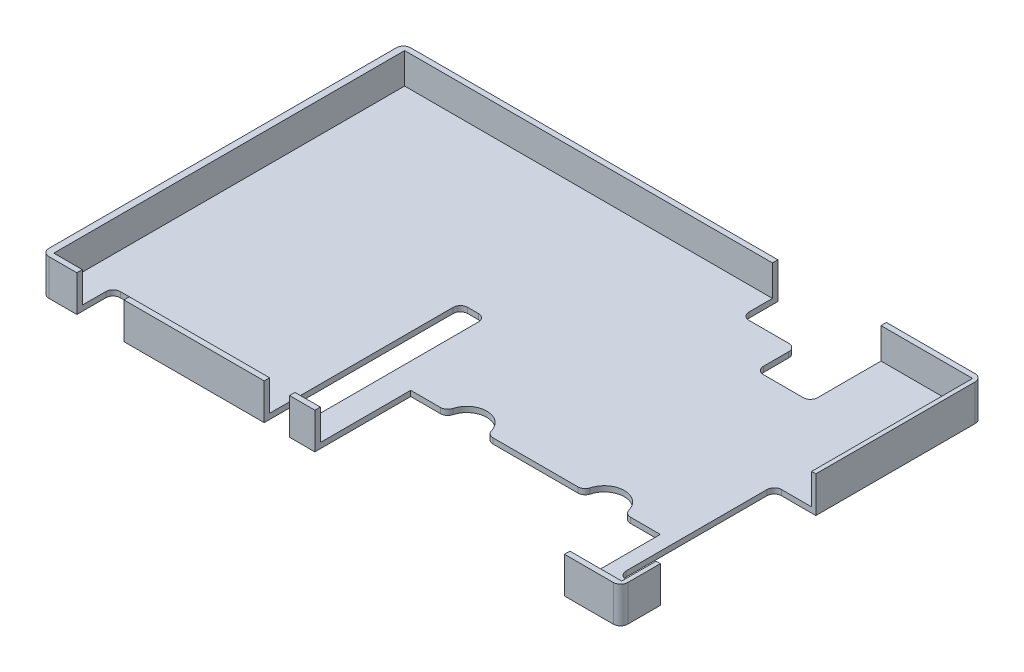
SolidWorks part; units mm, degrees
ref_plane "Front Plane" through (0, 0, 0) normal (0, 0, 1) x (1, 0, 0)
ref_plane "Top Plane" through (0, 0, 0) normal (0, 1, 0) x (1, 0, 0)
ref_plane "Right Plane" through (0, 0, 0) normal (1, 0, 0) x (0, 0, -1)
sketch "Sketch1" plane through (0, 0, 0) normal (0, 1, 0) x (1, 0, 0)
  line L1 (0, 0) -> (160, 0)
  line L2 (0, 0) -> (0, 100)
  line L3 (0, 100) -> (160, 100)
  line L4 (160, 0) -> (160, 100)
  dimension "D1" = 160
  dimension "D2" = 100
extrude "Boss-Extrude1" add sketch "Sketch1" along normal blind 1.5
sketch "Sketch2" plane through (0, 0, 0) normal (0, 1, 0) x (1, 0, 0)
  line L0 (160, 78.8862) -> (158.8264, 78.8862) construction
  line L1 (160, 0) -> (0, 0)
  line L2 (160, 0) -> (160, 100)
  line L3 (160, 100) -> (0, 100)
  line L4 (0, 0) -> (0, 100)
  line L5 (158.8264, 100) -> (158.8264, 98.5) construction
  line L7 (158.8264, 98.5) -> (1.8264, 98.5)
  line L8 (158.8264, 98.5) -> (158.8264, 1.5)
  line L9 (158.8264, 1.5) -> (1.8264, 1.5)
  line L10 (1.8264, 98.5) -> (1.8264, 1.5)
  dimension "D1" = 157
  dimension "D2" = 97
extrude "Boss-Extrude2" add sketch "Sketch2" along normal blind 10
fillet "Fillet1" radius 2 4 edges at (0, 5, -100) (160, 5, -100) (160, 5, 0) (0, 5, 0)
sketch "Sketch4" plane through (0, 0, 0) normal (0, -1, 0) x (1, 0, 0)
  line L0 (160, -94.7257) -> (133.5, -94.7257) construction
  line L1 (160, -2) -> (160, -98) construction
  line L2 (158, -100) -> (2, -100) construction
  line L3 (133.5, -100) -> (118.5, -100)
  line L4 (133.5, -100) -> (133.5, -79)
  line L5 (133.5, -79) -> (118.5, -79)
  line L6 (118.5, -100) -> (118.5, -79)
  dimension "D1" = 26.5
  dimension "D2" = 21
  dimension "D3" = 15
extrude "Cut-Extrude1" cut sketch "Sketch4" against normal through all
sketch "Sketch5" plane through (0, 0, 0) normal (0, -1, 0) x (1, 0, 0)
  line L0 (160, -9.2111) -> (144.5, -9.2111) construction
  line L1 (160, -2) -> (160, -98) construction
  line L2 (144.5, 0) -> (144.5, -26.5) construction
  line L3 (2, 0) -> (158, 0) construction
  line L5 (144.5, 0) -> (75.5, 0)
  line L6 (144.5, 0) -> (144.5, -26.5)
  line L7 (144.5, -26.5) -> (75.5, -26.5)
  line L8 (75.5, 0) -> (75.5, -26.5)
  dimension "D1" = 15.5
  dimension "D2" = 26.5
  dimension "D3" = 69
extrude "Cut-Extrude2" cut sketch "Sketch5" against normal through all
sketch "Sketch6" plane through (0, 0, 0) normal (0, -1, 0) x (1, 0, 0)
  line L0 (151.25, 0) -> (151.25, -11) construction
  line L1 (144.5, 0) -> (158, 0) construction
  line L2 (160, -11) -> (148.5, -11) construction
  line L3 (160, -2) -> (160, -98) construction
  line L5 (148.5, -11) -> (160, -11)
  line L6 (148.5, -11) -> (148.5, -54)
  line L7 (148.5, -54) -> (160, -54)
  line L8 (160, -11) -> (160, -54)
  dimension "D1" = 11
  dimension "D2" = 11.5
  dimension "D3" = 43
extrude "Cut-Extrude3" cut sketch "Sketch6" against normal through all
sketch "Sketch7" plane through (0, 0, 0) normal (0, -1, 0) x (1, 0, 0)
  line L0 (75.5, -13.25) -> (68.5, -13.25) construction
  line L1 (75.5, 0) -> (75.5, -26.5) construction
  line L2 (68.5, 0) -> (68.5, 0.75) construction
  line L3 (2, 0) -> (75.5, 0) construction
  line L5 (68.5, 0.75) -> (61.5, 0.75)
  line L6 (68.5, 0.75) -> (68.5, -54.25)
  line L7 (68.5, -54.25) -> (61.5, -54.25)
  line L8 (61.5, 0.75) -> (61.5, -54.25)
  point P11 (61.5, 0)
  dimension "D1" = 7
  dimension "D2" = 7
  dimension "D3" = 55
extrude "Cut-Extrude4" cut sketch "Sketch7" against normal blind 10
sketch "Sketch9" plane through (0, 0, 0) normal (0, -1, 0) x (1, 0, 0)
  line L0 (160, -11) -> (160, -54) construction
  line L1 (160, -26.5) -> (129, -26.5) construction
  line L2 (75.5, -26.5) -> (144.5, -26.5) construction
  line L3 (134.5394, -26.5) -> (123.4606, -26.5)
  line L4 (129, -26.5) -> (91, -26.5) construction
  line L6 (96.539, -26.5) -> (85.461, -26.5)
  arc A0 (134.5394, -26.5) -> (123.4606, -26.5) centre (129, -26.5) cw
  arc A1 (96.539, -26.5) -> (85.461, -26.5) centre (91, -26.5) cw
  dimension "D1" = 38
extrude "Cut-Extrude5" cut sketch "Sketch9" against normal blind 10
fillet "Fillet2" radius 2 4 edges at (96.539, 0.75, -26.5) (85.461, 0.75, -26.5) (123.4606, 0.75, -26.5) (134.5394, 0.75, -26.5)
sketch "Sketch10" plane through (0, 0, 0) normal (0, -1, 0) x (1, 0, 0)
  line L0 (2, 0) -> (61.5, 0) construction
  line L1 (22.7088, 0) -> (9.7088, 0)
  line L2 (22.7088, 0) -> (22.7088, -10)
  line L3 (22.7088, -10) -> (9.7088, -10)
  line L4 (9.7088, 0) -> (9.7088, -10)
  dimension "D1" = 13
  dimension "D2" = 10
extrude "Cut-Extrude6" cut sketch "Sketch10" against normal blind 10
fillet "Fillet3" radius 2 4 edges at (68.5, 0.75, -54.25) (61.5, 0.75, -54.25) (9.7088, 0.75, -10) (22.7088, 0.75, -10)
fillet "Fillet4" radius 2 4 edges at (148.5, 0.75, -11) (148.5, 0.75, -54) (133.5, 0.75, -79) (118.5, 0.75, -79)
sketch "Sketch11" plane through (0, 0, 0) normal (0, -1, 0) x (1, 0, 0)
  line L1 (118.5, -100) -> (103.5, -100)
  line L2 (118.5, -100) -> (118.5, -90)
  line L3 (118.5, -90) -> (103.5, -90)
  line L4 (103.5, -100) -> (103.5, -90)
  dimension "D1" = 15
  dimension "D2" = 10
extrude "Cut-Extrude7" cut sketch "Sketch11" against normal blind 10
fillet "Fillet5" radius 2 2 edges at (118.5, 0.75, -90) (103.5, 0.75, -90)
